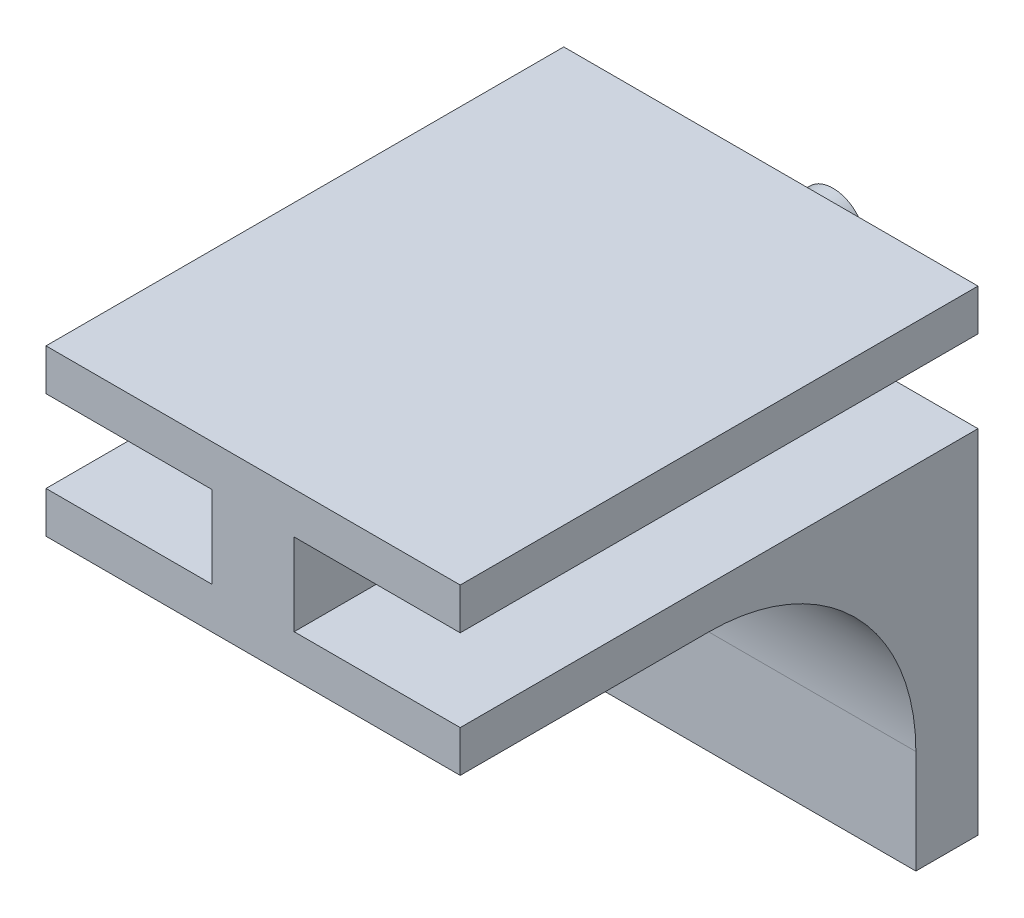
SolidWorks part; units mm, degrees
ref_plane "Front Plane" through (0, 0, 0) normal (0, 0, 1) x (1, 0, 0)
ref_plane "Top Plane" through (0, 0, 0) normal (0, 1, 0) x (1, 0, 0)
ref_plane "Right Plane" through (0, 0, 0) normal (1, 0, 0) x (0, 0, -1)
sketch "Sketch1" plane through (0, 0, 0) normal (0, 0, 1) x (1, 0, 0)
  line L0 (-49.3361, 0) -> (44.9688, 0) construction
  line L1 (0, 33.7475) -> (0, -43.3998) construction
  line L2 (10, -3.9812) -> (-10, -3.9812)
  line L3 (-10, -3.9812) -> (-10, -1.9812)
  line L4 (-10, -1.9812) -> (-1.9812, -1.9812)
  line L5 (-1.9812, -1.9812) -> (-1.9812, 1.9812)
  line L6 (-10, 1.9812) -> (-1.9812, 1.9812)
  line L7 (-10, 3.9812) -> (-10, 1.9812)
  line L8 (10, 3.9812) -> (-10, 3.9812)
  line L9 (10, 3.9812) -> (10, 1.9812)
  line L10 (10, 1.9812) -> (1.9812, 1.9812)
  line L11 (1.9812, -1.9812) -> (1.9812, 1.9812)
  line L12 (10, -1.9812) -> (1.9812, -1.9812)
  line L13 (10, -3.9812) -> (10, -1.9812)
  point P5 (1.9812, 0)
  point P11 (-1.9812, 0)
  point P15 (0, 3.9812)
  point P20 (0, -3.9812)
  dimension "D1" = 3.9624
  dimension "D2" = 20
  dimension "D3" = 2
  dimension "D4" = 3.9624
extrude "Boss-Extrude1" add sketch "Sketch1" along normal blind 25
sketch "Sketch2" plane through (0, -3.9812, 0) normal (0, -1, 0) x (1, 0, 0)
  line L0 (-10, 0) -> (-10, 3)
  line L1 (-10, 25) -> (-10, 0) construction
  line L2 (-10, 3) -> (10, 3)
  line L3 (10, 25) -> (10, 0) construction
  line L4 (10, 3) -> (10, 0)
  line L5 (10, 0) -> (-10, 0)
  dimension "D1" = 3
extrude "Boss-Extrude2" add sketch "Sketch2" along normal blind 15
fillet "Fillet1" radius 10 1 edges
sketch "Sketch3" plane through (0, 0, 0) normal (0, 0, -1) x (-1, 0, 0)
  circle A0 centre (0, 0) radius 1.5748
  dimension "D1" = 3.1496
extrude "Boss-Extrude3" add sketch "Sketch3" along normal blind 3
